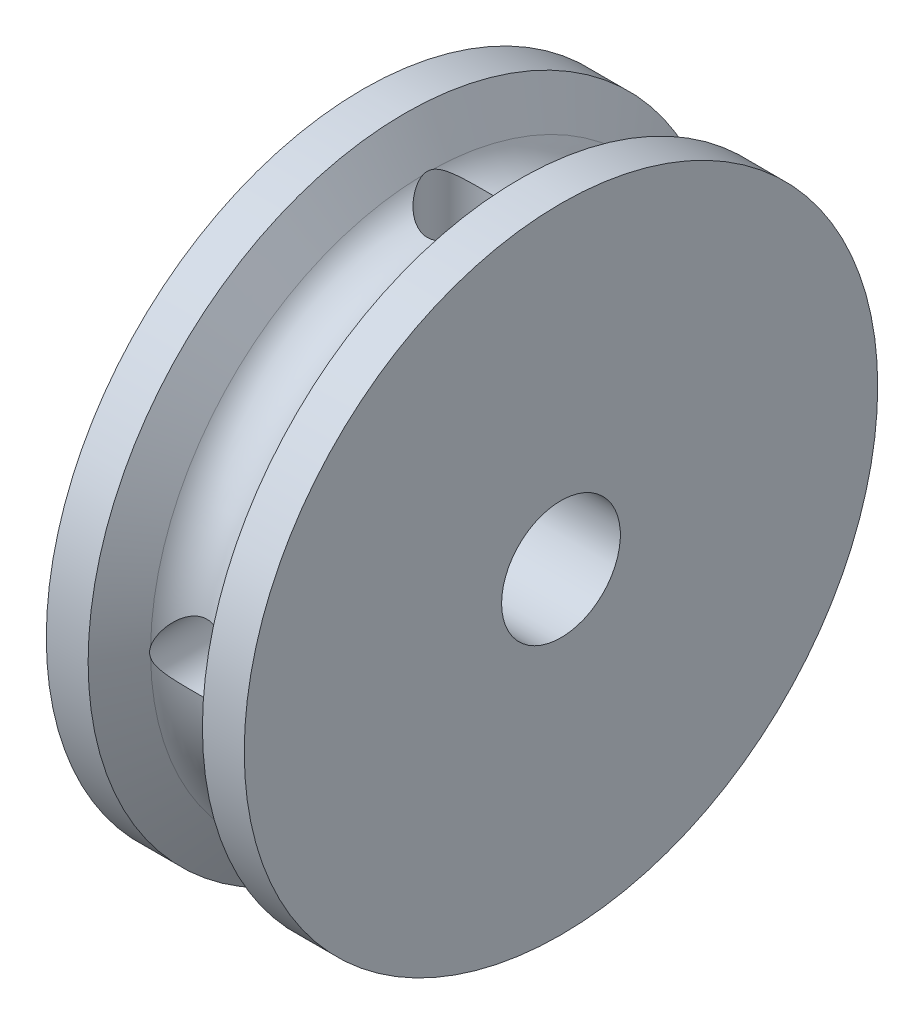
SolidWorks part; units mm, degrees
ref_plane "正面" through (0, 0, 0) normal (0, 0, 1) x (1, 0, 0)
ref_plane "平面" through (0, 0, 0) normal (0, 1, 0) x (1, 0, 0)
ref_plane "右側面" through (0, 0, 0) normal (1, 0, 0) x (0, 0, -1)
ref_axis "x軸" through (-88.99, 0, 0) along (1, 0, 0)
ref_axis "y軸" through (0, 55, 0) along (0, -1, 0)
ref_axis "z軸" through (0, 0, -88.99) along (0, 0, 1)
sketch "ｽｹｯﾁ1" plane through (0, 0, 0) normal (0, 0, 1) x (1, 0, 0)
  line L0 (-76.1578, 0) -> (84.3209, 0) construction
  line L1 (-88.99, 0) -> (88.99, 0) construction
  line L8 (5, 16) -> (5, 3)
  line L11 (0, 75.6717) -> (0, -54.01) construction
  line L12 (0, 55) -> (0, -55) construction
  line L13 (5, 3) -> (-5, 3)
  line L14 (-0.751, 15) -> (3.8611, 15) construction
  line L15 (5, 16) -> (2.8868, 16)
  line L16 (0, 11) -> (7.9433, 24.7583) construction
  line L17 (2.8868, 16) -> (1.7321, 14)
  line L18 (-2.8868, 16) -> (-1.7321, 14)
  line L19 (-5, 16) -> (-5, 3)
  line L20 (-5, 16) -> (-2.8868, 16)
  arc A0 (-1.7321, 14) -> (1.7321, 14) centre (0, 15) ccw
  point P20 (0, 3)
  dimension "D4" = 4
  dimension "D5" = 13
  dimension "D1" = 16
  dimension "D2" = 3
  dimension "D3" = 5
  dimension "D6" = 15
  dimension "D7" = 30
revolve "回転1" add sketch "ｽｹｯﾁ1" angle 360 about L0
ref_plane "平面1" through (0, 13, 0) normal (0, 1, 0) x (1, 0, 0)
sketch "ｽｹｯﾁ2" plane through (0, 13, 0) normal (0, 1, 0) x (1, 0, 0)
  circle A0 centre (0, 0) radius 1.75
  dimension "D1" = 3.5
extrude "ｶｯﾄ - 押し出し1" cut sketch "ｽｹｯﾁ2" against normal blind 5 and the other way through all
sketch "ｽｹｯﾁ3" plane through (0, 8, 0) normal (0, 1, 0) x (1, 0, 0)
  point P0 (0, 0)
hole_wizard "M3x0.5 ねじ穴1" positions "3Dｽｹｯﾁ1" profile "ｽｹｯﾁ4" tap size "M3x0.5" standard "JIS" end condition up to next
sketch3d "3Dｽｹｯﾁ1"
  point P0 (0, 0, 0)
  point P3 (0, 0, 0)
  point P5 (0, 8, 0)
sketch "ｽｹｯﾁ4" plane through (0, 8, 0) normal (1, 0, 0) x (0, 0, 1)
  line L0 (0, 0) -> (0, 8)
  line L1 (0, 8) -> (1.25, 8)
  line L2 (1.25, 8) -> (1.25, 0)
  line L5 (1.25, 0) -> (0, 0)
  line L11 (0, -6.35) -> (0, 107.95) construction
  dimension "次ｻｰﾌｪｽまでのねじ下穴ﾄﾞﾘﾙ直径" = 2.5
  dimension "次ｻｰﾌｪｽまでのねじ下穴ﾄﾞﾘﾙの深さ" = 8
cosmetic thread "穴のねじ山1" parameters "D2"=3
cosmetic thread "穴のねじ山2" parameters "D2"=3
cosmetic thread "穴のねじ山3" parameters "D2"=3
pattern_circular "円形ﾊﾟﾀｰﾝ1" count 2 every 90 about axis through (-88.99, 0, 0) along (1, 0, 0) of "M3x0.5 ねじ穴1", "ｶｯﾄ - 押し出し1"
